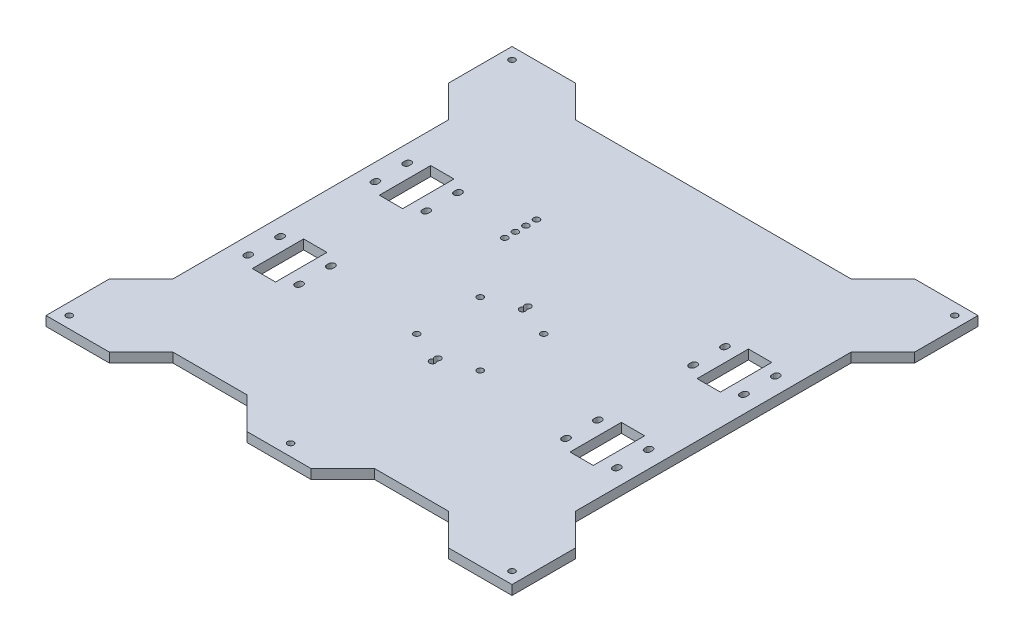
SolidWorks part; units mm, degrees
ref_plane "Front Plane" through (0, 0, 0) normal (0, 0, 1) x (1, 0, 0)
ref_plane "Top Plane" through (0, 0, 0) normal (0, 1, 0) x (1, 0, 0)
ref_plane "Right Plane" through (0, 0, 0) normal (1, 0, 0) x (0, 0, -1)
sketch "Sketch1" plane through (0, 0, 0) normal (0, 1, 0) x (1, 0, 0)
  line L1 (-110, 110) -> (110, 110)
  line L2 (-110, 110) -> (-110, -110)
  line L3 (-110, -110) -> (110, -110)
  line L4 (110, 110) -> (110, -110)
  line L5 (-110, 110) -> (110, -110) construction
  line L6 (-110, -110) -> (110, 110) construction
  point P0 (0, 0)
  dimension "D1" = 220
  dimension "D2" = 220
extrude "Square" add sketch "Sketch1" along normal blind 4.5
sketch "Sketch2" plane through (0, 4.5, 0) normal (0, 1, 0) x (1, 0, 0)
  line L0 (0, 110) -> (0, -110) construction
  line L1 (110, 110) -> (-110, 110) construction
  line L2 (-110, -110) -> (110, -110) construction
  line L3 (-110, 0) -> (110, 0) construction
  line L4 (-110, 110) -> (-110, -110) construction
  line L5 (110, -110) -> (110, 110) construction
  line L6 (75, 110) -> (75, -110) construction
  line L7 (75, 30) -> (0, 30) construction
  line L8 (75, -30) -> (0, -30) construction
  circle A0 centre (87, 38) radius 1.45
  circle A1 centre (87, 22) radius 1.45
  circle A2 centre (63, 22) radius 1.45
  circle A3 centre (63, 38) radius 1.45
  circle A4 centre (-63, 38) radius 1.45
  circle A5 centre (-63, 22) radius 1.45
  circle A6 centre (-87, 22) radius 1.45
  circle A7 centre (-87, 38) radius 1.45
  circle A8 centre (-87, 22) radius 1.45
  circle A9 centre (-87, 38) radius 1.45
  circle A10 centre (-63, 38) radius 1.45
  circle A11 centre (-63, 22) radius 1.45
  circle A12 centre (63, 22) radius 1.45
  circle A13 centre (63, 38) radius 1.45
  circle A14 centre (87, 38) radius 1.45
  circle A15 centre (87, 22) radius 1.45
  circle A16 centre (87, -22) radius 1.45
  circle A17 centre (87, -38) radius 1.45
  circle A18 centre (63, -38) radius 1.45
  circle A19 centre (63, -22) radius 1.45
  circle A20 centre (-63, -22) radius 1.45
  circle A21 centre (-63, -38) radius 1.45
  circle A22 centre (-87, -38) radius 1.45
  circle A23 centre (-87, -22) radius 1.45
  circle A24 centre (-87, -38) radius 1.45
  circle A25 centre (-87, -22) radius 1.45
  circle A26 centre (-63, -22) radius 1.45
  circle A27 centre (-63, -38) radius 1.45
  circle A28 centre (63, -38) radius 1.45
  circle A29 centre (63, -22) radius 1.45
  circle A30 centre (87, -22) radius 1.45
  circle A31 centre (87, -38) radius 1.45
  dimension "D6" = 2.9
  dimension "D7" = 2.9
  dimension "D1" = 75
  dimension "D2" = 30
  dimension "D3" = 16
  dimension "D5" = 12
extrude "LM8UU-Holders" cut sketch "Sketch2" against normal through all contours A7 | A6 | A5 | A4 | A20 | A21 | A22 | A23 | A19 | A18 | A17 | A16 | A1 | A0 | A3 | A2 region at (87, 4.5, -38) region at (87, 4.5, -22) region at (63, 4.5, -22) region at (63, 4.5, -38) region at (-63, 4.5, -38) region at (-63, 4.5, -22) region at (-87, 4.5, -22) region at (-87, 4.5, -38) region at (87, 4.5, 22) region at (87, 4.5, 38) region at (63, 4.5, 38) region at (63, 4.5, 22) region at (-63, 4.5, 22) region at (-63, 4.5, 38) region at (-87, 4.5, 38) region at (-87, 4.5, 22)
sketch "Sketch10" plane through (0, 4.5, 0) normal (0, 1, 0) x (1, 0, 0)
  line L0 (0, 110) -> (0, -79.9796) construction
  line L3 (-26.5242, 0) -> (110, 0) construction
  line L6 (75, 110) -> (75, -110) construction
  line L7 (75, 30) -> (-75, 30) construction
  line L8 (87, 22) -> (87, 23) construction
  line L9 (110, 110) -> (-110, 110) construction
  line L10 (110, -110) -> (110, 110) construction
  line L11 (85.55, 22) -> (85.55, 23)
  line L12 (88.45, 22) -> (88.45, 23)
  line L13 (87, 38) -> (87, 37) construction
  line L14 (88.45, 38) -> (88.45, 37)
  line L15 (85.55, 38) -> (85.55, 37)
  line L16 (63, 38) -> (63, 37) construction
  line L17 (61.55, 38) -> (61.55, 37)
  line L18 (64.45, 38) -> (64.45, 37)
  line L19 (63, 22) -> (63, 23) construction
  line L20 (64.45, 22) -> (64.45, 23)
  line L21 (61.55, 22) -> (61.55, 23)
  line L22 (75, -30) -> (-75, -30) construction
  line L23 (87, -22) -> (87, -23) construction
  line L24 (85.55, -22) -> (85.55, -23)
  line L25 (88.45, -22) -> (88.45, -23)
  line L26 (87, -38) -> (87, -37) construction
  line L27 (88.45, -38) -> (88.45, -37)
  line L28 (85.55, -38) -> (85.55, -37)
  line L29 (63, -38) -> (63, -37) construction
  line L30 (61.55, -38) -> (61.55, -37)
  line L31 (64.45, -38) -> (64.45, -37)
  line L32 (63, -22) -> (63, -23) construction
  line L33 (64.45, -22) -> (64.45, -23)
  line L34 (61.55, -22) -> (61.55, -23)
  line L35 (26.5242, 0) -> (-110, 0) construction
  line L36 (-87, 22) -> (-87, 23) construction
  line L37 (-85.55, 22) -> (-85.55, 23)
  line L38 (-88.45, 22) -> (-88.45, 23)
  line L39 (-87, 38) -> (-87, 37) construction
  line L40 (-88.45, 38) -> (-88.45, 37)
  line L41 (-85.55, 38) -> (-85.55, 37)
  line L42 (-63, 38) -> (-63, 37) construction
  line L43 (-61.55, 38) -> (-61.55, 37)
  line L44 (-64.45, 38) -> (-64.45, 37)
  line L45 (-63, 22) -> (-63, 23) construction
  line L46 (-64.45, 22) -> (-64.45, 23)
  line L47 (-61.55, 22) -> (-61.55, 23)
  line L48 (-87, -22) -> (-87, -23) construction
  line L49 (-85.55, -22) -> (-85.55, -23)
  line L50 (-88.45, -22) -> (-88.45, -23)
  line L51 (-87, -38) -> (-87, -37) construction
  line L52 (-88.45, -38) -> (-88.45, -37)
  line L53 (-85.55, -38) -> (-85.55, -37)
  line L54 (-63, -38) -> (-63, -37) construction
  line L55 (-61.55, -38) -> (-61.55, -37)
  line L56 (-64.45, -38) -> (-64.45, -37)
  line L57 (-63, -22) -> (-63, -23) construction
  line L58 (-64.45, -22) -> (-64.45, -23)
  line L59 (-61.55, -22) -> (-61.55, -23)
  arc A0 (61.55, 38) -> (64.45, 38) centre (63, 38) cw
  arc A1 (88.45, 38) -> (85.55, 38) centre (87, 38) ccw
  arc A2 (85.55, 22) -> (88.45, 22) centre (87, 22) ccw
  arc A3 (88.45, 23) -> (85.55, 23) centre (87, 23) ccw
  arc A4 (85.55, 37) -> (88.45, 37) centre (87, 37) ccw
  arc A5 (64.45, 37) -> (61.55, 37) centre (63, 37) cw
  arc A6 (64.45, 22) -> (61.55, 22) centre (63, 22) cw
  arc A7 (61.55, 23) -> (64.45, 23) centre (63, 23) cw
  arc A8 (85.55, -22) -> (88.45, -22) centre (87, -22) cw
  arc A9 (88.45, -23) -> (85.55, -23) centre (87, -23) cw
  arc A10 (88.45, -38) -> (85.55, -38) centre (87, -38) cw
  arc A11 (85.55, -37) -> (88.45, -37) centre (87, -37) cw
  arc A12 (61.55, -38) -> (64.45, -38) centre (63, -38) ccw
  arc A13 (64.45, -37) -> (61.55, -37) centre (63, -37) ccw
  arc A14 (64.45, -22) -> (61.55, -22) centre (63, -22) ccw
  arc A15 (61.55, -23) -> (64.45, -23) centre (63, -23) ccw
  arc A16 (-85.55, 22) -> (-88.45, 22) centre (-87, 22) cw
  arc A17 (-88.45, 23) -> (-85.55, 23) centre (-87, 23) cw
  arc A18 (-88.45, 38) -> (-85.55, 38) centre (-87, 38) cw
  arc A19 (-85.55, 37) -> (-88.45, 37) centre (-87, 37) cw
  arc A20 (-61.55, 38) -> (-64.45, 38) centre (-63, 38) ccw
  arc A21 (-64.45, 37) -> (-61.55, 37) centre (-63, 37) ccw
  arc A22 (-64.45, 22) -> (-61.55, 22) centre (-63, 22) ccw
  arc A23 (-61.55, 23) -> (-64.45, 23) centre (-63, 23) ccw
  arc A24 (-85.55, -22) -> (-88.45, -22) centre (-87, -22) ccw
  arc A25 (-88.45, -23) -> (-85.55, -23) centre (-87, -23) ccw
  arc A26 (-88.45, -38) -> (-85.55, -38) centre (-87, -38) ccw
  arc A27 (-85.55, -37) -> (-88.45, -37) centre (-87, -37) ccw
  arc A28 (-61.55, -38) -> (-64.45, -38) centre (-63, -38) cw
  arc A29 (-64.45, -37) -> (-61.55, -37) centre (-63, -37) cw
  arc A30 (-64.45, -22) -> (-61.55, -22) centre (-63, -22) cw
  arc A31 (-61.55, -23) -> (-64.45, -23) centre (-63, -23) cw
  point P8 (87, 22.5)
  point P19 (87, 37.5)
  point P28 (63, 37.5)
  point P35 (63, 22.5)
  point P44 (87, -22.5)
  point P51 (87, -37.5)
  point P58 (63, -37.5)
  point P65 (63, -22.5)
  point P73 (0, 30)
  point P74 (0, -30)
  point P76 (-87, 22.5)
  point P83 (-87, 37.5)
  point P90 (-63, 37.5)
  point P97 (-63, 22.5)
  point P104 (-87, -22.5)
  point P111 (-87, -37.5)
  point P118 (-63, -37.5)
  point P125 (-63, -22.5)
  dimension "D1" = 75
  dimension "D2" = 30
  dimension "D3" = 16
  dimension "D5" = 12
  dimension "D4" = 1.45
  dimension "D7" = 1.45
  dimension "D8" = 1
  dimension "D9" = 1
sketch "Sketch3" plane through (0, 4.5, 0) normal (0, 1, 0) x (1, 0, 0)
  line L0 (0, -110) -> (0, 110) construction
  line L1 (-110, -110) -> (110, -110) construction
  line L2 (110, 110) -> (-110, 110) construction
  line L3 (110, -15) -> (-110, -15) construction
  line L6 (15, -30) -> (-15, -30) construction
  line L7 (15, 0) -> (-15, 0) construction
  line L8 (110, -110) -> (110, 110) construction
  line L9 (-110, 110) -> (-110, -110) construction
  line L10 (110, 0) -> (-110, 0) construction
  circle A0 centre (-15, -30) radius 1.45
  circle A1 centre (15, -30) radius 1.45
  circle A2 centre (15, 0) radius 1.45
  circle A3 centre (-15, 0) radius 1.45
  point P16 (0, -30)
  dimension "D1" = 2.9
  dimension "D2" = 15
  dimension "D3" = 15
  dimension "D5" = 15
extrude "DefaultBelt" cut sketch "Sketch3" against normal through all
sketch "Sketch4" plane through (0, 4.5, 0) normal (0, 1, 0) x (1, 0, 0)
  line L0 (0, 110) -> (0, -110) construction
  line L1 (110, 110) -> (-110, 110) construction
  line L2 (-110, -110) -> (110, -110) construction
  line L3 (-15, -1.45) -> (-15, -28.55) construction
  line L4 (15, -28.55) -> (15, -1.45) construction
  line L5 (15, -15) -> (-15, -15) construction
  arc A0 (-0.7348, 6.25) -> (0.7348, 6.25) centre (0, 5) ccw
  arc A1 (0.7348, 6.25) -> (-0.7348, 6.25) centre (0, 7.5) ccw
  arc A2 (0.7348, -36.25) -> (-0.7348, -36.25) centre (0, -37.5) cw
  arc A3 (-0.7348, -36.25) -> (0.7348, -36.25) centre (0, -35) cw
  circle A4 centre (-15, 0) radius 1.45 construction
  circle A5 centre (-15, -30) radius 1.45 construction
  circle A6 centre (15, -30) radius 1.45 construction
  circle A7 centre (15, 0) radius 1.45 construction
  dimension "D1" = 2.9
  dimension "D2" = 2.9
  dimension "D3" = 20
  dimension "D4" = 22.5
extrude "BeltOptions" cut sketch "Sketch4" against normal through all
sketch "Sketch5" plane through (0, 4.5, 0) normal (0, 1, 0) x (1, 0, 0)
  line L0 (-110, 0) -> (110, 0) construction
  line L1 (-110, 110) -> (-110, -110) construction
  line L2 (110, -110) -> (110, 110) construction
  line L3 (0, 110) -> (0, -110) construction
  line L4 (110, 110) -> (-110, 110) construction
  line L5 (-110, 110) -> (-110, 80)
  line L6 (-110, 80) -> (-95, 65)
  line L7 (-95, 65) -> (-95, -65)
  line L8 (0, 0) -> (-110, 110) construction
  line L9 (-65, 95) -> (65, 95)
  line L10 (-80, 110) -> (-65, 95)
  line L11 (-110, 110) -> (-80, 110)
  line L12 (-95, 65) -> (-95, -65)
  line L13 (0, 0) -> (110, 110) construction
  line L14 (95, 65) -> (95, -65)
  line L15 (110, 110) -> (80, 110)
  line L16 (80, 110) -> (65, 95)
  line L17 (95, 65) -> (95, -65)
  line L18 (110, 80) -> (95, 65)
  line L19 (110, 110) -> (110, 80)
  line L20 (0, 0) -> (110, -110) construction
  line L21 (0, 0) -> (-110, -110) construction
  line L22 (110, -110) -> (110, -80)
  line L23 (110, -80) -> (95, -65)
  line L24 (80, -110) -> (65, -95)
  line L25 (110, -110) -> (80, -110)
  line L26 (-110, -110) -> (-80, -110)
  line L27 (-80, -110) -> (-65, -95)
  line L28 (-65, -95) -> (65, -95)
  line L29 (-110, -80) -> (-95, -65)
  line L30 (-110, -110) -> (-110, -80)
  point P24 (0, 95)
  point P32 (95, 0)
  point P35 (-95, 0)
  point P36 (0, -95)
  circle M16 centre (15, -30) radius 1.45
  circle M18 centre (63, 38) radius 1.45
  circle M20 centre (87, 22) radius 1.45
  circle M22 centre (87, -38) radius 1.45
  circle M23 centre (63, -38) radius 1.45
  circle M24 centre (63, -22) radius 1.45
  circle M25 centre (-87, -22) radius 1.45
  circle M26 centre (-87, -38) radius 1.45
  circle M27 centre (-63, -38) radius 1.45
  circle M28 centre (-63, -22) radius 1.45
  circle M29 centre (-63, 38) radius 1.45
  circle M30 centre (-63, 22) radius 1.45
  circle M31 centre (-87, 22) radius 1.45
  circle M32 centre (-87, 38) radius 1.45
  line M33 (110, -110) -> (110, 110)
  line M34 (110, 110) -> (-110, 110)
  line M35 (-110, 110) -> (-110, -110)
  line M36 (-110, -110) -> (110, -110)
  dimension "D1" = 15
  dimension "D2" = 30
  dimension "D3" = 45
  dimension "D4" = 45
extrude "Shaping" cut sketch "Sketch5" against normal blind 10 flip side to cut contours L29 L27 L28 L24 L23 L14 L18 L16 L9 L10 L6 L7 M35 M36 M33 M34 M16 M18 M20 M22 M24 M26 M28 M30 M32 M31 M29 M27 M25 M23 region at (0.037, 4.5, -0.0113)
sketch "Sketch6" plane through (0, 4.5, 0) normal (0, 1, 0) x (1, 0, 0)
  line L0 (-110, 110) -> (110, -110) construction
  line L1 (-110, -110) -> (110, 110) construction
  line L2 (110, 80) -> (110, 110) construction
  line L3 (0, 95) -> (0, -95) construction
  line L4 (-65, 95) -> (65, 95) construction
  line L5 (-65, -95) -> (65, -95) construction
  line L6 (-95, 0) -> (95, 0) construction
  line L7 (-95, 65) -> (-95, -65) construction
  line L8 (95, 65) -> (95, -65) construction
  circle A0 centre (-104.5, 104.5) radius 1.45
  circle A1 centre (104.5, 104.5) radius 1.45
  circle A2 centre (104.5, -104.5) radius 1.45
  circle A3 centre (-104.5, -104.5) radius 1.45
  dimension "D2" = 2.9
  dimension "D1" = 45
  dimension "D3" = 104.5
extrude "Cut-Extrude5" cut sketch "Sketch6" against normal through all
sketch "Sketch7" plane through (0, 4.5, 0) normal (0, 1, 0) x (1, 0, 0)
  line L0 (-87, 38) -> (-63, 22) construction
  line L1 (-63, 22) -> (-87, 22) construction
  line L2 (-87, 22) -> (-63, 38) construction
  line L3 (-63, 38) -> (-87, 38) construction
  line L4 (-95, 0) -> (95, 0) construction
  line L5 (-80.5, 42.125) -> (-69.5, 42.125)
  line L6 (-80.5, 42.125) -> (-80.5, 17.875)
  line L7 (-80.5, 17.875) -> (-69.5, 17.875)
  line L8 (-69.5, 42.125) -> (-69.5, 17.875)
  line L9 (-80.5, 42.125) -> (-69.5, 17.875) construction
  line L10 (-80.5, 17.875) -> (-69.5, 42.125) construction
  line L11 (-95, 65) -> (-95, -65) construction
  line L12 (95, 65) -> (95, -65) construction
  line L13 (0, -95) -> (0, 95) construction
  line L14 (-65, -95) -> (65, -95) construction
  line L15 (-65, 95) -> (65, 95) construction
  line L16 (-80.5, -17.875) -> (-69.5, -42.125) construction
  line L17 (-80.5, -42.125) -> (-69.5, -17.875) construction
  line L18 (-63, -38) -> (-87, -38) construction
  line L19 (-87, -22) -> (-63, -38) construction
  line L20 (-63, -22) -> (-87, -22) construction
  line L21 (-87, -38) -> (-63, -22) construction
  line L22 (-69.5, -42.125) -> (-69.5, -17.875)
  line L23 (-80.5, -17.875) -> (-69.5, -17.875)
  line L24 (-80.5, -42.125) -> (-80.5, -17.875)
  line L25 (-80.5, -42.125) -> (-69.5, -42.125)
  line L26 (-80.5, 17.875) -> (-69.5, 42.125) construction
  line L27 (80.5, 17.875) -> (69.5, 42.125) construction
  line L28 (87, -38) -> (63, -22) construction
  line L29 (63, -22) -> (87, -22) construction
  line L30 (87, -22) -> (63, -38) construction
  line L31 (63, -38) -> (87, -38) construction
  line L32 (80.5, -42.125) -> (69.5, -17.875) construction
  line L33 (80.5, -17.875) -> (69.5, -42.125) construction
  line L34 (80.5, 17.875) -> (69.5, 42.125) construction
  line L35 (80.5, 42.125) -> (69.5, 17.875) construction
  line L36 (63, 38) -> (87, 38) construction
  line L37 (87, 22) -> (63, 38) construction
  line L38 (63, 22) -> (87, 22) construction
  line L39 (87, 38) -> (63, 22) construction
  line L40 (80.5, -42.125) -> (69.5, -42.125)
  line L41 (80.5, -42.125) -> (80.5, -17.875)
  line L42 (80.5, -17.875) -> (69.5, -17.875)
  line L43 (69.5, -42.125) -> (69.5, -17.875)
  line L44 (69.5, 42.125) -> (69.5, 17.875)
  line L45 (80.5, 17.875) -> (69.5, 17.875)
  line L46 (80.5, 42.125) -> (80.5, 17.875)
  line L47 (80.5, 42.125) -> (69.5, 42.125)
  point P4 (-75, 30)
  point P33 (-75, -30)
  point P50 (75, -30)
  point P51 (75, 30)
  dimension "D1" = 11
  dimension "D2" = 24.25
extrude "Cut-Extrude6" cut sketch "Sketch7" against normal through all
sketch "Sketch8" plane through (0, 4.5, 0) normal (0, 1, 0) x (1, 0, 0)
  line L3 (-65, 95) -> (65, 95) construction
  line L4 (-33.45, 45) -> (-33.45, 30) construction
  circle A0 centre (-33.45, 45) radius 1.45
  circle A1 centre (-33.45, 40) radius 1.45
  circle A2 centre (-33.45, 35) radius 1.45
  circle A3 centre (-33.45, 30) radius 1.45
  dimension "D1" = 2.9
  dimension "D2" = 50
extrude "EndstopTrigger" cut sketch "Sketch8" against normal through all
pattern_linear "LPattern1" [suppressed] count 2 spacing 30 of bodies 108
sketch "Sketch9" plane through (0, 4.5, 0) normal (0, 1, 0) x (1, 0, 0)
  line L0 (-80, -110) -> (80, -110) construction
  line L1 (0, -110) -> (0, -95) construction
  line L2 (-65, -95) -> (65, -95) construction
  line L3 (15, -110) -> (-15, -110)
  line L4 (-15, -110) -> (-30, -95)
  line L5 (-30, -95) -> (30, -95)
  line L6 (-80, -110) -> (-65, -95) construction
  line L9 (15, -110) -> (30, -95)
  line L10 (-104.5, -104.5) -> (104.5, -104.5) construction
  circle A0 centre (0, -104.5) radius 1.45
  dimension "D2" = 15
  dimension "D3" = 2.9
  dimension "D1" = 90
extrude "Boss-Extrude1" add sketch "Sketch9" against normal through all
extrude "HolesToSlots" cut sketch "Sketch10" against normal through all
equation "\"X-ROD-SPACING\"=45"
equation "\"Y-ROD-SPACING\"=75"
equation "\"Z-ROD-SPACING\"=17.5"
equation "\"Y-BED-OFFSET\"=2"
equation "\"Y-BED-ROD-INSET\"=3.5"
equation "\"T-SLOT-NUT-FILLET-RADIUS\"=0.5"
equation "\"T-SLOT-SCREW-SHAFT-RADIUS\"=1.55"
equation "\"T-SLOT-SCREW-SHAFT-CUTOUT-LENGTH\"=11.0"
equation "\"T-SLOT-NUT-DEPTH\"=3.5"
equation "\"T-SLOT-NUT-WIDTH\"=2.85"
equation "\"T-SLOT-NUT-END-DISTANCE\"=8"
equation "\"ACRYLIC-THICKNESS\"=10"
equation "\"ACRYLIC-THICKNESS2\"=4.5"
equation "\"ACRYLIC-TAB-CUTOUT-SIZE\"=\"ACRYLIC-THICKNESS\"+\"ACRYLIC-TAB-TOLERANCE\"*2"
equation "\"ACRYLIC-TAB-WIDTH\"=\"ACRYLIC-THICKNESS\""
equation "\"ACRYLIC-M3-HOLE\"=2.9"
equation "\"SMOOTHROD-CAP-SCREW-DISTANCE\"=20"
equation "\"FRAME-WIDTH-INNER\"=370"
equation "\"NEMA17-HOLE-SPACING\"=31"
equation "\"NEMA17-CENTRAL-CUTOUT\"=22.5"
equation "\"Z-BRACKET-REACH\"=55"
equation "\"TOP-BRACKET-SPACING\"=40"
equation "\"SMOOTHROD-X-LENGTH\"=350"
equation "\"SMOOTHROD-Y-LENGTH\"=350"
equation "\"SMOOTHROD-Z-LENGTH\"=350"
equation "\"SMOOTHROD-TIGHTENING-HEADROOM\"=.25"
equation "\"LEADSCREW-Z-LENGTH\"=300"
equation "\"SCREW-LENGTH-FRAME\"=\"ACRYLIC-THICKNESS\" + 10"
equation "\"SCREW-HEAD-RADIUS\"=6"
equation "\"PRINTED-X-SMOOTHROD-DIAMETER\"=8.4"
equation "\"PRINTED-X-SMOOTHROD-CUTOUT\"=10"
equation "\"PRINTED-X-BASE-HEIGHT\"=10"
equation "\"PRINTED-LM8UU-CUTOUT-SIZE\"=15.5"
equation "\"PRINTED-LM8UU-CUTOUT-LENGTH\"=24.5"
equation "\"PRINTED-X-IDLER-HEIGHT\"=16"
equation "\"PSU-MOUNTING-WIDTH\"=95"
equation "\"PSU-MOUNTING-HEIGHT\"=177"
equation "\"Y-BELT-TO-ROD-DISTANCE\"=20"
equation "\"D6@Sketch2\"=\"ACRYLIC-M3-HOLE\""
equation "\"D7@Sketch2\"=\"ACRYLIC-M3-HOLE\""
equation "\"D1@Sketch2\"=\"Y-ROD-SPACING\""
equation "\"D1@Sketch3\"=\"ACRYLIC-M3-HOLE\""
equation "\"D2@Sketch6\"=\"ACRYLIC-M3-HOLE\""
equation "\"Y-BED-SCREW-SPACING\"=209"
equation "\"Y-BED-SCREW-CUTOUT-SLOT-HEIGHT\"=2"
equation "\"ACRYLIC-TAB-TOLERANCE\"=-.05"
equation "\"Z-ROD-INSET\"=16"
equation "\"SCREW-LENGTH-MOTOR\"=\"ACRYLIC-THICKNESS\" + 5"
equation "\"SCREW-LENGTH-EXTRUDER\"=28"
equation "\"PRINTED-M3-HOLE\"=3.5"
equation "\"SPOOL-HOLDER-ROD-SPACING\"=150"
equation "\"ACRYLIC-X-CARRIAGE-WIDTH\"=55"
equation "\"ACRYLIC-X-CARRIAGE-HEIGHT\"=75"
equation "\"ACRYLIC-X-CARRIAGE-LM8UU-CUTOUT-WIDTH\"=24.25"
equation "\"ACRYLIC-X-CARRIAGE-LM8UU-CUTOUT-HEIGHT\"=11.0"
equation "\"ACRYLIC-X-CARRIAGE-SCREW-SPACING-X\"=15"
equation "\"ACRYLIC-X-CARRIAGE-SCREW-SPACING-Y\"=33"
equation "\"ACRYLIC-X-CARRIAGE-CENTER-TAB-SPACING\"=14"
equation "\"ACRYLIC-X-CARRIAGE-EXTRUDER-OFFSET\"=26"
equation "\"ACRYLIC-X-CARRIAGE-EXTRUDER-ANGLE\"=90"
equation "\"ACRYLIC-X-CARRIAGE-EXTRUDER-SHELF-DEPTH\"=\"ACRYLIC-X-CARRIAGE-EXTRUDER-OFFSET\" + 28"
equation "\"ACRYLIC-X-CARRIAGE-EXTRUDER-BRACE-SPACING\"=23"
equation "\"ACRYLIC-X-CARRIAGE-EXTRUDER-BRACE-TAB-OFFSET\"=20"
equation "\"ACRYLIC-X-CARRIAGE-EXTRUDER-BRACE-HEIGHT\"=35"
equation "\"ACRYLIC-X-CARRIAGE-EXTRUDER-BRACE-SCREW-SPACING\"=22"
equation "\"ACRYLIC-X-CARRIAGE-DUAL-WIDTH-MULTIPLIER\"=1.65"
equation "\"ACRYLIC-X-CARRIAGE-DUAL-HOTEND-SPACING\"=42"
equation "\"ACRYLIC-X-CARRIAGE-DUAL-WIDTH\"=75"
equation "\"ACRYLIC-X-CARRIAGE-DUAL-HOTEND-SEPARATION\"=36"
equation "\"ACRYLIC-X-CARRIAGE-DUAL-MOUNT-PLATE-DEPTH\"=75"
equation "\"ACRYLIC-X-CARRIAGE-DUAL-MOUNT-BRACE-WIDTH\"=33"
equation "\"ACRYLIC-X-CARRIAGE-DUAL-MOUNT-SCREW-WIDTH\"=40"
equation "\"BLOWER-FAN-WIDTH\"=15"
equation "\"D1@Sketch7\"=\"ACRYLIC-X-CARRIAGE-LM8UU-CUTOUT-HEIGHT\""
equation "\"D2@Sketch7\"=\"ACRYLIC-X-CARRIAGE-LM8UU-CUTOUT-WIDTH\""
equation "\"D1@Sketch8\"=\"ACRYLIC-M3-HOLE\""
equation "\"D2@Sketch4\"=\"ACRYLIC-M3-HOLE\""
equation "\"D1@Sketch4\"=\"ACRYLIC-M3-HOLE\""
equation "\"D3@Sketch4\"=20"
equation "\"D3@Sketch9\"=\"ACRYLIC-M3-HOLE\""
equation "\"D4@Sketch10\"=\"ACRYLIC-M3-HOLE\"/2"
equation "\"D7@Sketch10\"=\"ACRYLIC-M3-HOLE\" / 2"
